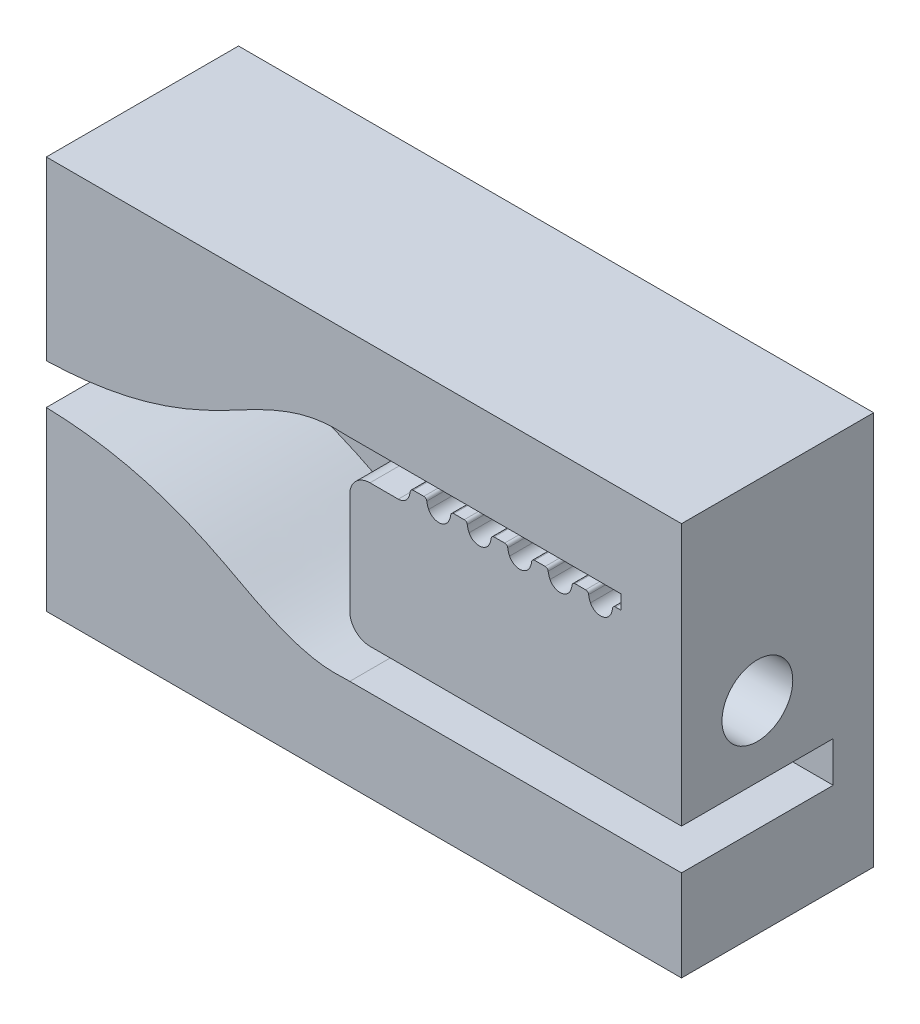
SolidWorks part; units mm, degrees
ref_plane "Piano frontale" through (0, 0, 0) normal (0, 0, 1) x (1, 0, 0)
ref_plane "Piano superiore" through (0, 0, 0) normal (0, 1, 0) x (1, 0, 0)
ref_plane "Piano destro" through (0, 0, 0) normal (1, 0, 0) x (0, 0, -1)
sketch "Schizzo1" plane through (0, 0, 0) normal (0, 0, 1) x (1, 0, 0)
  line L0 (31.4, 19.45) -> (31.4, 6.5)
  line L1 (26.4, 14.25) -> (26.6598, 14.25)
  line L2 (31.4, 19.45) -> (0, 19.45)
  line L3 (31.4, 4.5) -> (31.4, 0)
  line L4 (27.4, 14.25) -> (27.4, 13.5) construction
  line L5 (28.4, 14.25) -> (28.1402, 14.25)
  line L6 (31.4, 0) -> (0, 0)
  line L7 (0, 0) -> (0, 8.725)
  line L8 (0, 10.725) -> (0, 8.725) construction
  line L9 (15, 4.5) -> (31.4, 4.5)
  line L10 (28.4, 14.95) -> (28.4, 14.25)
  line L11 (24.4, 14.25) -> (24.6598, 14.25)
  line L12 (25.4, 14.25) -> (25.4, 13.5) construction
  line L13 (26.4, 14.25) -> (26.1402, 14.25)
  line L14 (17.4, 6.5) -> (31.4, 6.5)
  line L15 (0, 19.45) -> (0, 10.725)
  line L16 (0, 9.725) -> (31.4, 9.725) construction
  line L17 (15, 14.95) -> (28.4, 14.95)
  line L18 (22.4, 14.25) -> (22.6598, 14.25)
  line L19 (23.4, 14.25) -> (23.4, 13.5) construction
  line L20 (24.4, 14.25) -> (24.1402, 14.25)
  line L21 (20.4, 14.25) -> (20.6598, 14.25)
  line L22 (21.4, 14.25) -> (21.4, 13.5) construction
  line L23 (22.4, 14.25) -> (22.1402, 14.25)
  line L24 (18.4, 14.25) -> (18.6598, 14.25)
  line L25 (19.4, 14.25) -> (19.4, 13.5) construction
  line L26 (20.4, 14.25) -> (20.1402, 14.25)
  line L27 (17.4, 13.5) -> (15, 13.5)
  line L28 (17.4, 14.25) -> (17.4, 13.5) construction
  line L29 (18.4, 14.25) -> (18.1402, 14.25)
  line L30 (27, 14.25) -> (25, 14.25) construction
  line L31 (15, 13.5) -> (15, 6.5)
  line L32 (15, 6.5) -> (17.4, 6.5)
  line L71 (16.4, 14.25) -> (16.6598, 14.25) [skipped]
  arc A0 (26.9011, 13.8118) -> (27.8989, 13.8118) centre (27.4, 14.055) ccw
  arc A1 (27.8989, 13.8118) -> (27.9915, 14.1196) centre (27, 14.25) ccw
  arc A2 (27.9915, 14.1196) -> (28.1402, 14.25) centre (28.1402, 14.1) cw
  arc A3 (26.8085, 14.1196) -> (26.6598, 14.25) centre (26.6598, 14.1) ccw
  arc A4 (26.9011, 13.8118) -> (26.8085, 14.1196) centre (27.8, 14.25) cw
  arc A5 (24.9011, 13.8118) -> (25.8989, 13.8118) centre (25.4, 14.055) ccw
  arc A6 (25.8989, 13.8118) -> (25.9915, 14.1196) centre (25, 14.25) ccw
  arc A7 (25.9915, 14.1196) -> (26.1402, 14.25) centre (26.1402, 14.1) cw
  arc A8 (24.8085, 14.1196) -> (24.6598, 14.25) centre (24.6598, 14.1) ccw
  arc A9 (24.9011, 13.8118) -> (24.8085, 14.1196) centre (25.8, 14.25) cw
  arc A10 (22.9011, 13.8118) -> (23.8989, 13.8118) centre (23.4, 14.055) ccw
  arc A11 (23.8989, 13.8118) -> (23.9915, 14.1196) centre (23, 14.25) ccw
  arc A12 (23.9915, 14.1196) -> (24.1402, 14.25) centre (24.1402, 14.1) cw
  arc A13 (22.8085, 14.1196) -> (22.6598, 14.25) centre (22.6598, 14.1) ccw
  arc A14 (22.9011, 13.8118) -> (22.8085, 14.1196) centre (23.8, 14.25) cw
  arc A15 (20.9011, 13.8118) -> (21.8989, 13.8118) centre (21.4, 14.055) ccw
  arc A16 (21.8989, 13.8118) -> (21.9915, 14.1196) centre (21, 14.25) ccw
  arc A17 (21.9915, 14.1196) -> (22.1402, 14.25) centre (22.1402, 14.1) cw
  arc A18 (20.8085, 14.1196) -> (20.6598, 14.25) centre (20.6598, 14.1) ccw
  arc A19 (20.9011, 13.8118) -> (20.8085, 14.1196) centre (21.8, 14.25) cw
  arc A20 (18.9011, 13.8118) -> (19.8989, 13.8118) centre (19.4, 14.055) ccw
  arc A21 (19.8989, 13.8118) -> (19.9915, 14.1196) centre (19, 14.25) ccw
  arc A22 (19.9915, 14.1196) -> (20.1402, 14.25) centre (20.1402, 14.1) cw
  arc A23 (18.8085, 14.1196) -> (18.6598, 14.25) centre (18.6598, 14.1) ccw
  arc A24 (18.9011, 13.8118) -> (18.8085, 14.1196) centre (19.8, 14.25) cw
  arc A25 (17.4, 13.5) -> (17.8989, 13.8118) centre (17.4, 14.055) ccw
  arc A26 (17.8989, 13.8118) -> (17.9915, 14.1196) centre (17, 14.25) ccw
  arc A27 (17.9915, 14.1196) -> (18.1402, 14.25) centre (18.1402, 14.1) cw
  arc A95 (16.8085, 14.1196) -> (16.6598, 14.25) centre (16.6598, 14.1) ccw [skipped]
  arc A96 (16.9011, 13.8118) -> (16.8085, 14.1196) centre (17.8, 14.25) cw [skipped]
  spline S0 degree 3 poles (15, 14.95) (14.1986, 14.95) (12.2061, 15.353) (5.4367, 10.8794) (0, 10.725) knots 0 0 0 0 0.572771 1 1 1 1
  spline S1 degree 3 poles (15, 4.5) (14.1986, 4.5) (12.2061, 4.097) (5.4367, 8.5706) (0, 8.725) knots 0 0 0 0 0.572771 1 1 1 1
  point P5 (27, 14.25)
  point P33 (25, 14.25)
  point P49 (23, 14.25)
  point P65 (21, 14.25)
  point P81 (19, 14.25)
  point P97 (17, 14.25)
  dimension "D4" = 0.555
  dimension "D5" = 1
  dimension "D6" = 0.15
  dimension "D1" = 2
  dimension "D2" = 0.7
  dimension "D3" = 0.4
  dimension "D7" = 1
  dimension "D8" = 2
  dimension "D9" = 3
  dimension "D11" = 7
  dimension "D12" = 4.5
  dimension "D13" = 4.5
  dimension "D14" = 0.75
  dimension "D10" = 2.4
  dimension "D15" = 2
  dimension "D16" = 15
extrude "Estrusione-Estrusione1" add sketch "Schizzo1" along normal blind 7.5 contours L9 S1 L7 L6 L3 | S0 L17 L10 L5 A2 A1 A0 A4 A3 L1 L13 A7 A6 A5 A9 A8 L11 L20 A12 A11 A10 A14 A13 L18 L23 A17 A16 A15 A19 A18 L21 L26 A22 A21 A20 A24 A23 L24 L29 A27 A26 A25 L14 L0 L2 L15 region at (31.0603, 12.975, 0) region at (13.5381, 3.0146, 0)
sketch "Schizzo2" plane through (0, 0, 0) normal (0, 0, -1) x (-1, 0, 0)
  line L1 (0, 0) -> (-31.4, 0)
  line L2 (0, 0) -> (0, 19.45)
  line L3 (0, 19.45) -> (-31.4, 19.45)
  line L4 (-31.4, 0) -> (-31.4, 19.45)
extrude "Estrusione-Estrusione2" add sketch "Schizzo2" along normal blind 2
sketch "Schizzo5" plane through (15, 0, 0) normal (-1, 0, 0) x (0, 0, 1)
  line L0 (7.5, 10) -> (0, 10) construction
  line L1 (7.5, 13.5) -> (7.5, 6.5) construction
  line L2 (0, 13.5) -> (0, 6.5) construction
  line L4 (6.9832, 10) -> (5.3088, 12.9)
  line L5 (2.1912, 12.9) -> (2.1912, 13.5)
  line L6 (2.1912, 12.9) -> (0.5168, 10)
  line L7 (0.5168, 10) -> (1.9802, 7.4654)
  line L8 (7.5, 13.5) -> (0, 13.5) construction
  line L9 (5.3088, 7.1) -> (6.9832, 10)
  line L10 (1.9133, 7.2) -> (5.262, 7.2) [skipped]
  line L11 (5.5867, 12.8) -> (2.238, 12.8) [skipped]
  line L12 (2.1912, 13.5) -> (5.3088, 13.5)
  line L13 (5.3088, 13.5) -> (5.3088, 12.9)
  line L14 (1.9802, 7.4654) -> (1.9802, 6.5)
  line L15 (7.5, 6.5) -> (0, 6.5) construction
  line L16 (1.9802, 6.5) -> (5.3088, 6.5)
  line L17 (5.3088, 6.5) -> (5.3088, 7.1)
  circle A0 centre (3.75, 10) radius 2.8 construction
  circle A1 centre (3.75, 10) radius 1.75
  line M9 (0, 6.5) -> (7.5, 6.5)
  line M11 (7.5, 13.5) -> (0, 13.5)
  dimension "D1" = 5.6
  dimension "D6" = 3.5
  dimension "D2" = 3.3486
  dimension "D3" = 0.6
  dimension "D4" = 0.6
  dimension "D5" = 0.6
extrude "Taglio-Estrusione3" cut sketch "Schizzo5" against normal blind 2.4 contours A1 | L17 L9 L4 L13 L5 L6 L7 L14 A1 M9 M11 region at (15, 8.5976, 6.0635) region at (15, 10, 3.75)
extrude "Taglio-Estrusione4" cut sketch "Schizzo5<3>" against normal through all contours A1 region at (15, 10, 3.75)
sketch "Schizzo5<3>" plane through (15, 0, 0) normal (-1, 0, 0) x (0, 0, 1) same geometry as "Schizzo5"
fillet "Raccordo1" radius 1 4 edges at (15, 13.5, 6.4044) (15, 13.5, 1.0956) (15, 6.5, 0.9901) (15, 6.5, 6.4044)
